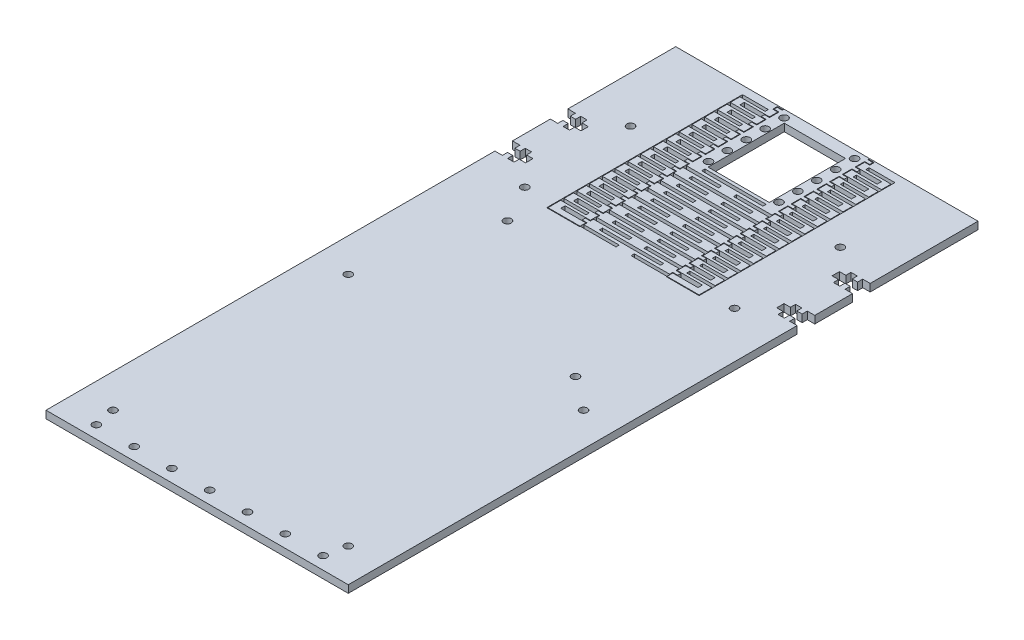
SolidWorks part; units mm, degrees
ref_plane "Front Plane" through (0, 0, 0) normal (0, 0, 1) x (1, 0, 0)
ref_plane "Top Plane" through (0, 0, 0) normal (0, 1, 0) x (1, 0, 0)
ref_plane "Right Plane" through (0, 0, 0) normal (1, 0, 0) x (0, 0, -1)
sketch "Sketch1" plane through (0, 0, 0) normal (0, 1, 0) x (1, 0, 0)
  line L0 (0, 250) -> (0, 0) construction
  line L1 (-60, 250) -> (60, 250)
  line L2 (-60, 250) -> (-60, 0)
  line L3 (-60, 0) -> (60, 0)
  line L4 (60, 250) -> (60, 0)
  circle A0 centre (46.7, 13.3) radius 1.5
  circle A3 centre (46.7, 106.7) radius 1.5
  circle A4 centre (-46.7, 13.3) radius 1.5
  circle A5 centre (-46.7, 106.7) radius 1.5
  circle A6 centre (-41.6382, 213.7) radius 1.5
  circle A7 centre (-41.6382, 171.7) radius 1.5
  circle A10 centre (41.6382, 171.7) radius 1.5
  circle A11 centre (41.6382, 213.7) radius 1.5
  circle A12 centre (33.5, 116.7) radius 1.5
  circle A13 centre (-33.5, 156.7) radius 1.5
  circle A14 centre (-45, 5) radius 1.5
  circle A15 centre (-30, 5) radius 1.5
  circle A16 centre (-15, 5) radius 1.5
  circle A17 centre (0, 5) radius 1.5
  circle A18 centre (45, 5) radius 1.5
  circle A19 centre (30, 5) radius 1.5
  circle A20 centre (15, 5) radius 1.5
  line B0 (-60, 207.1925) -> (-57.0282, 207.1925)
  line B1 (-57.0282, 207.1925) -> (-57.0282, 205.1605)
  line B2 (-57.0282, 205.1605) -> (-54.92, 205.1605)
  line B3 (-54.92, 205.1605) -> (-54.92, 207.1925)
  line B4 (-54.92, 207.1925) -> (-52.38, 207.1925)
  line B5 (-52.38, 207.1925) -> (-52.38, 205.1605)
  line B6 (-52.38, 205.1605) -> (-49.84, 205.1605)
  line B7 (-49.84, 205.1605) -> (-49.84, 202.2395)
  line B8 (-60, 200.2075) -> (-57.0282, 200.2075)
  line B9 (-57.0282, 200.2075) -> (-57.0282, 202.2395)
  line B10 (-57.0282, 202.2395) -> (-54.92, 202.2395)
  line B11 (-54.92, 202.2395) -> (-54.92, 200.2075)
  line B12 (-54.92, 200.2075) -> (-52.38, 200.2075)
  line B13 (-52.38, 200.2075) -> (-52.38, 202.2395)
  line B14 (-52.38, 202.2395) -> (-49.84, 202.2395)
  line B15 (-60, 185.1925) -> (-57.0282, 185.1925)
  line B16 (-57.0282, 185.1925) -> (-57.0282, 183.1605)
  line B17 (-57.0282, 183.1605) -> (-54.92, 183.1605)
  line B18 (-54.92, 183.1605) -> (-54.92, 185.1925)
  line B19 (-54.92, 185.1925) -> (-52.38, 185.1925)
  line B20 (-52.38, 185.1925) -> (-52.38, 183.1605)
  line B21 (-52.38, 183.1605) -> (-49.84, 183.1605)
  line B22 (-49.84, 183.1605) -> (-49.84, 180.2395)
  line B23 (-60, 178.2075) -> (-57.0282, 178.2075)
  line B24 (-57.0282, 178.2075) -> (-57.0282, 180.2395)
  line B25 (-57.0282, 180.2395) -> (-54.92, 180.2395)
  line B26 (-54.92, 180.2395) -> (-54.92, 178.2075)
  line B27 (-54.92, 178.2075) -> (-52.38, 178.2075)
  line B28 (-52.38, 178.2075) -> (-52.38, 180.2395)
  line B29 (-52.38, 180.2395) -> (-49.84, 180.2395)
  line B30 (60, 185.1925) -> (57.0282, 185.1925)
  line B31 (57.0282, 185.1925) -> (57.0282, 183.1605)
  line B32 (57.0282, 183.1605) -> (54.92, 183.1605)
  line B33 (54.92, 183.1605) -> (54.92, 185.1925)
  line B34 (54.92, 185.1925) -> (52.38, 185.1925)
  line B35 (52.38, 185.1925) -> (52.38, 183.1605)
  line B36 (52.38, 183.1605) -> (49.84, 183.1605)
  line B37 (49.84, 183.1605) -> (49.84, 180.2395)
  line B38 (60, 178.2075) -> (57.0282, 178.2075)
  line B39 (57.0282, 178.2075) -> (57.0282, 180.2395)
  line B40 (57.0282, 180.2395) -> (54.92, 180.2395)
  line B41 (54.92, 180.2395) -> (54.92, 178.2075)
  line B42 (54.92, 178.2075) -> (52.38, 178.2075)
  line B43 (52.38, 178.2075) -> (52.38, 180.2395)
  line B44 (52.38, 180.2395) -> (49.84, 180.2395)
  line B45 (60, 207.1925) -> (57.0282, 207.1925)
  line B46 (57.0282, 207.1925) -> (57.0282, 205.1605)
  line B47 (57.0282, 205.1605) -> (54.92, 205.1605)
  line B48 (54.92, 205.1605) -> (54.92, 207.1925)
  line B49 (54.92, 207.1925) -> (52.38, 207.1925)
  line B50 (52.38, 207.1925) -> (52.38, 205.1605)
  line B51 (52.38, 205.1605) -> (49.84, 205.1605)
  line B52 (49.84, 205.1605) -> (49.84, 202.2395)
  line B53 (60, 200.2075) -> (57.0282, 200.2075)
  line B54 (57.0282, 200.2075) -> (57.0282, 202.2395)
  line B55 (57.0282, 202.2395) -> (54.92, 202.2395)
  line B56 (54.92, 202.2395) -> (54.92, 200.2075)
  line B57 (54.92, 200.2075) -> (52.38, 200.2075)
  line B58 (52.38, 200.2075) -> (52.38, 202.2395)
  line B59 (52.38, 202.2395) -> (49.84, 202.2395)
  dimension "D3" = 3
  dimension "D8" = 3
  dimension "D1" = 120
  dimension "D2" = 250
  dimension "D4" = 13.3
  dimension "D5" = 13.3
  dimension "D6" = 93.4
  dimension "D7" = 42
  dimension "D9" = 18.3618
  dimension "D10" = 15
  dimension "D11" = 33.5
  dimension "D12" = 67
  dimension "D13" = 40
  dimension "D14" = 10
  dimension "D15" = 10
  dimension "D16" = 10
  dimension "D17" = 15
  dimension "D18" = 15
  dimension "D19" = 15
  dimension "D20" = 5
sketch_block_instance "Block4-1"
sketch_block "Block4" parameters "D1"=1.4605, "D2"=2.9718
sketch_block_instance "Block4-2"
sketch_block_instance "Block4-3"
sketch_block_instance "Block4-4"
extrude "Boss-Extrude1" add sketch "Sketch1" along normal blind 2.9718 contours L1 L0 L3 L4 A11 A0 A3 A10 A12 | L0 L1 L2 B0 B1 B2 B3 B4 B5 B6 B7 B14 B13 B12 B11 B10 B9 B8 B15 B16 B17 B18 B19 B20 B21 B22 B29 B28 B27 B26 B25 B24 B23 L3 A13 A7 A6 A4 A5 region at (0, 0, -124.7167)
sketch "Sketch2" plane through (0, 2.9718, 0) normal (0, 1, 0) x (1, 0, 0)
  line L0 (-30, 250) -> (-30, 165) construction
  line L1 (-60, 250) -> (60, 250) construction
  line L2 (-30, 165) -> (30, 165) construction
  line L3 (30, 165) -> (30, 250) construction
  line L4 (0, 250) -> (0, 0) construction
  line L5 (-17, 250) -> (17, 250)
  line L7 (-17, 215) -> (17, 215)
  line L8 (17, 250) -> (17, 215)
  line L10 (-12.15, 215) -> (12.15, 215)
  line L11 (-12.15, 215) -> (-12.15, 245.25)
  line L12 (-12.15, 245.25) -> (12.15, 245.25)
  line L13 (12.15, 215) -> (12.15, 245.25)
  line L14 (-12.15, 213.73) -> (12.15, 213.73)
  line L15 (-12.15, 213.73) -> (-12.15, 212.46)
  line L16 (-12.15, 212.46) -> (12.15, 212.46)
  line L17 (12.15, 213.73) -> (12.15, 212.46)
  line L18 (-17, 211.19) -> (-3, 211.19)
  line L20 (-17, 209.92) -> (-3, 209.92)
  line L21 (-3, 211.19) -> (-3, 209.92)
  line L22 (3, 211.19) -> (3, 209.92)
  line L23 (17, 209.92) -> (3, 209.92)
  line L24 (17, 211.19) -> (3, 211.19)
  line L25 (12.15, 215) -> (12.15, 245.25)
  line L26 (-17, 217.54) -> (-17, 216.27)
  line L27 (17.25, 250) -> (17.25, 249.54)
  line L28 (-17, 215) -> (-17, 213.73)
  line L29 (-17, 213.73) -> (-19, 213.73)
  line L30 (-19, 213.73) -> (-19, 212.46)
  line L31 (-19, 212.46) -> (-17, 212.46)
  line L32 (-17, 212.46) -> (-17, 211.19)
  line L33 (-17.25, 215) -> (-17.25, 213.98)
  line L34 (-17.25, 213.98) -> (-19.25, 213.98)
  line L35 (-30.25, 250) -> (-30.25, 165)
  line L36 (-19.25, 212.21) -> (-17.25, 212.21)
  line L37 (-17.25, 212.21) -> (-17.25, 211.19)
  line L38 (19, 213.73) -> (19, 212.46)
  line L39 (19, 212.46) -> (17, 212.46)
  line L40 (17, 212.46) -> (17, 211.19)
  line L41 (17, 215) -> (17, 213.73)
  line L42 (17, 213.73) -> (19, 213.73)
  line L43 (19.25, 213.98) -> (19.25, 212.21)
  line L44 (19.25, 212.21) -> (17.25, 212.21)
  line L45 (17.25, 212.21) -> (17.25, 211.19)
  line L46 (17.25, 213.98) -> (19.25, 213.98)
  line L47 (17.25, 215) -> (17.25, 213.98)
  line L48 (-17.25, 211.19) -> (-17.25, 209.92)
  line L49 (17.25, 211.19) -> (17.25, 209.92)
  line L50 (-17.25, 209.92) -> (-17.25, 208.9)
  line L51 (-17, 209.92) -> (-17, 208.65)
  line L52 (17.25, 250) -> (17, 250)
  line L53 (-17, 250) -> (-17.25, 250)
  line L54 (-17, 208.65) -> (-19, 208.65)
  line L55 (-17.25, 208.9) -> (-19.25, 208.9)
  line L56 (-19, 208.65) -> (-19, 207.38)
  line L57 (-30, 250) -> (-30, 246.75)
  line L58 (-19, 207.38) -> (-17, 207.38)
  line L59 (-19.25, 207.13) -> (-17.25, 207.13)
  line L60 (-17, 207.38) -> (-17, 206.11)
  line L61 (-17, 206.11) -> (-3, 206.11)
  line L62 (-17, 204.84) -> (-3, 204.84)
  line L63 (-17.25, 206.11) -> (-17.25, 204.84)
  line L64 (-12.15, 207.38) -> (12.15, 207.38)
  line L65 (-17.25, 207.13) -> (-17.25, 206.11)
  line L66 (-3, 206.11) -> (-3, 204.84)
  line L67 (17, 206.11) -> (3, 206.11)
  line L68 (3, 206.11) -> (3, 204.84)
  line L69 (17, 204.84) -> (3, 204.84)
  line L70 (-12.15, 208.65) -> (12.15, 208.65)
  line L71 (-12.15, 208.65) -> (-12.15, 207.38)
  line L72 (12.15, 208.65) -> (12.15, 207.38)
  line L73 (17.25, 209.92) -> (17.25, 208.9)
  line L74 (17, 209.92) -> (17, 208.65)
  line L75 (17.25, 208.9) -> (19.25, 208.9)
  line L76 (17, 208.65) -> (19, 208.65)
  line L77 (19.25, 208.9) -> (19.25, 207.13)
  line L78 (19, 208.65) -> (19, 207.38)
  line L79 (19, 207.38) -> (17, 207.38)
  line L80 (19.25, 207.13) -> (17.25, 207.13)
  line L81 (17, 207.38) -> (17, 206.11)
  line L82 (17.25, 207.13) -> (17.25, 206.11)
  line L83 (17.25, 206.11) -> (17.25, 204.84)
  line L84 (-17.25, 204.84) -> (-17.25, 203.82)
  line L85 (-17, 204.84) -> (-17, 203.57)
  line L86 (-17, 203.57) -> (-19, 203.57)
  line L87 (-17.25, 203.82) -> (-19.25, 203.82)
  line L88 (-19, 203.57) -> (-19, 202.3)
  line L89 (-30, 245.48) -> (-30, 241.67)
  line L90 (-19, 202.3) -> (-17, 202.3)
  line L91 (-19.25, 202.05) -> (-17.25, 202.05)
  line L92 (-17, 202.3) -> (-17, 201.03)
  line L93 (-17, 201.03) -> (-3, 201.03)
  line L94 (-17, 199.76) -> (-3, 199.76)
  line L95 (-17.25, 201.03) -> (-17.25, 199.76)
  line L96 (-12.15, 202.3) -> (12.15, 202.3)
  line L97 (-17.25, 202.05) -> (-17.25, 201.03)
  line L98 (-3, 201.03) -> (-3, 199.76)
  line L99 (17, 201.03) -> (3, 201.03)
  line L100 (3, 201.03) -> (3, 199.76)
  line L101 (17, 199.76) -> (3, 199.76)
  line L102 (-12.15, 203.57) -> (12.15, 203.57)
  line L103 (-12.15, 203.57) -> (-12.15, 202.3)
  line L104 (12.15, 203.57) -> (12.15, 202.3)
  line L105 (17.25, 204.84) -> (17.25, 203.82)
  line L106 (17, 204.84) -> (17, 203.57)
  line L107 (17.25, 203.82) -> (19.25, 203.82)
  line L108 (17, 203.57) -> (19, 203.57)
  line L109 (19.25, 203.82) -> (19.25, 202.05)
  line L110 (19, 203.57) -> (19, 202.3)
  line L111 (19, 202.3) -> (17, 202.3)
  line L112 (19.25, 202.05) -> (17.25, 202.05)
  line L113 (17, 202.3) -> (17, 201.03)
  line L114 (17.25, 202.05) -> (17.25, 201.03)
  line L115 (17.25, 201.03) -> (17.25, 199.76)
  line L116 (-17.25, 199.76) -> (-17.25, 198.74)
  line L117 (-17, 199.76) -> (-17, 198.49)
  line L118 (-17, 198.49) -> (-19, 198.49)
  line L119 (-17.25, 198.74) -> (-19.25, 198.74)
  line L120 (-19, 198.49) -> (-19, 197.22)
  line L121 (-30, 244.92) -> (-30, 241.67)
  line L122 (-19, 197.22) -> (-17, 197.22)
  line L123 (-19.25, 196.97) -> (-17.25, 196.97)
  line L124 (-17, 197.22) -> (-17, 195.95)
  line L125 (-17, 195.95) -> (-3, 195.95)
  line L126 (-17, 194.68) -> (-3, 194.68)
  line L127 (-17.25, 195.95) -> (-17.25, 194.68)
  line L128 (-12.15, 197.22) -> (12.15, 197.22)
  line L129 (-17.25, 196.97) -> (-17.25, 195.95)
  line L130 (-3, 195.95) -> (-3, 194.68)
  line L131 (17, 195.95) -> (3, 195.95)
  line L132 (3, 195.95) -> (3, 194.68)
  line L133 (17, 194.68) -> (3, 194.68)
  line L134 (-12.15, 198.49) -> (12.15, 198.49)
  line L135 (-12.15, 198.49) -> (-12.15, 197.22)
  line L136 (12.15, 198.49) -> (12.15, 197.22)
  line L137 (17.25, 199.76) -> (17.25, 198.74)
  line L138 (17, 199.76) -> (17, 198.49)
  line L139 (17.25, 198.74) -> (19.25, 198.74)
  line L140 (17, 198.49) -> (19, 198.49)
  line L141 (19.25, 198.74) -> (19.25, 196.97)
  line L142 (19, 198.49) -> (19, 197.22)
  line L143 (19, 197.22) -> (17, 197.22)
  line L144 (19.25, 196.97) -> (17.25, 196.97)
  line L145 (17, 197.22) -> (17, 195.95)
  line L146 (17.25, 196.97) -> (17.25, 195.95)
  line L147 (17.25, 195.95) -> (17.25, 194.68)
  line L148 (-17.25, 194.68) -> (-17.25, 193.66)
  line L149 (-17, 194.68) -> (-17, 193.41)
  line L150 (-17, 193.41) -> (-19, 193.41)
  line L151 (-17.25, 193.66) -> (-19.25, 193.66)
  line L152 (-19, 193.41) -> (-19, 192.14)
  line L153 (-30, 240.4) -> (-30, 236.59)
  line L154 (-19, 192.14) -> (-17, 192.14)
  line L155 (-19.25, 191.89) -> (-17.25, 191.89)
  line L156 (-17, 192.14) -> (-17, 190.87)
  line L157 (-17, 190.87) -> (-3, 190.87)
  line L158 (-17, 189.6) -> (-3, 189.6)
  line L159 (-17.25, 190.87) -> (-17.25, 189.6)
  line L160 (-12.15, 192.14) -> (12.15, 192.14)
  line L161 (-17.25, 191.89) -> (-17.25, 190.87)
  line L162 (-3, 190.87) -> (-3, 189.6)
  line L163 (17, 190.87) -> (3, 190.87)
  line L164 (3, 190.87) -> (3, 189.6)
  line L165 (17, 189.6) -> (3, 189.6)
  line L166 (-12.15, 193.41) -> (12.15, 193.41)
  line L167 (-12.15, 193.41) -> (-12.15, 192.14)
  line L168 (12.15, 193.41) -> (12.15, 192.14)
  line L169 (17.25, 194.68) -> (17.25, 193.66)
  line L170 (17, 194.68) -> (17, 193.41)
  line L171 (17.25, 193.66) -> (19.25, 193.66)
  line L172 (17, 193.41) -> (19, 193.41)
  line L173 (19.25, 193.66) -> (19.25, 191.89)
  line L174 (19, 193.41) -> (19, 192.14)
  line L175 (19, 192.14) -> (17, 192.14)
  line L176 (19.25, 191.89) -> (17.25, 191.89)
  line L177 (17, 192.14) -> (17, 190.87)
  line L178 (17.25, 191.89) -> (17.25, 190.87)
  line L179 (17.25, 190.87) -> (17.25, 189.6)
  line L180 (-17.25, 189.6) -> (-17.25, 188.58)
  line L181 (-17, 189.6) -> (-17, 188.33)
  line L182 (-17, 188.33) -> (-19, 188.33)
  line L183 (-17.25, 188.58) -> (-19.25, 188.58)
  line L184 (-19, 188.33) -> (-19, 187.06)
  line L185 (-30, 239.84) -> (-30, 236.59)
  line L186 (-19, 187.06) -> (-17, 187.06)
  line L187 (-19.25, 186.81) -> (-17.25, 186.81)
  line L188 (-17, 187.06) -> (-17, 185.79)
  line L189 (-17, 185.79) -> (-3, 185.79)
  line L190 (-17, 184.52) -> (-3, 184.52)
  line L191 (-17.25, 185.79) -> (-17.25, 184.52)
  line L192 (-12.15, 187.06) -> (12.15, 187.06)
  line L193 (-17.25, 186.81) -> (-17.25, 185.79)
  line L194 (-3, 185.79) -> (-3, 184.52)
  line L195 (17, 185.79) -> (3, 185.79)
  line L196 (3, 185.79) -> (3, 184.52)
  line L197 (17, 184.52) -> (3, 184.52)
  line L198 (-12.15, 188.33) -> (12.15, 188.33)
  line L199 (-12.15, 188.33) -> (-12.15, 187.06)
  line L200 (12.15, 188.33) -> (12.15, 187.06)
  line L201 (17.25, 189.6) -> (17.25, 188.58)
  line L202 (17, 189.6) -> (17, 188.33)
  line L203 (17.25, 188.58) -> (19.25, 188.58)
  line L204 (17, 188.33) -> (19, 188.33)
  line L205 (19.25, 188.58) -> (19.25, 186.81)
  line L206 (19, 188.33) -> (19, 187.06)
  line L207 (19, 187.06) -> (17, 187.06)
  line L208 (19.25, 186.81) -> (17.25, 186.81)
  line L209 (17, 187.06) -> (17, 185.79)
  line L210 (17.25, 186.81) -> (17.25, 185.79)
  line L211 (17.25, 185.79) -> (17.25, 184.52)
  line L212 (-17.25, 184.52) -> (-17.25, 183.5)
  line L213 (-17, 184.52) -> (-17, 183.25)
  line L214 (-17, 183.25) -> (-19, 183.25)
  line L215 (-17.25, 183.5) -> (-19.25, 183.5)
  line L216 (-19, 183.25) -> (-19, 181.98)
  line L217 (-30, 235.32) -> (-30, 231.51)
  line L218 (-19, 181.98) -> (-17, 181.98)
  line L219 (-19.25, 181.73) -> (-17.25, 181.73)
  line L220 (-17, 181.98) -> (-17, 180.71)
  line L221 (-17, 180.71) -> (-3, 180.71)
  line L222 (-17, 179.44) -> (-3, 179.44)
  line L223 (-17.25, 180.71) -> (-17.25, 179.44)
  line L224 (-12.15, 181.98) -> (12.15, 181.98)
  line L225 (-17.25, 181.73) -> (-17.25, 180.71)
  line L226 (-3, 180.71) -> (-3, 179.44)
  line L227 (17, 180.71) -> (3, 180.71)
  line L228 (3, 180.71) -> (3, 179.44)
  line L229 (17, 179.44) -> (3, 179.44)
  line L230 (-12.15, 183.25) -> (12.15, 183.25)
  line L231 (-12.15, 183.25) -> (-12.15, 181.98)
  line L232 (12.15, 183.25) -> (12.15, 181.98)
  line L233 (17.25, 184.52) -> (17.25, 183.5)
  line L234 (17, 184.52) -> (17, 183.25)
  line L235 (17.25, 183.5) -> (19.25, 183.5)
  line L236 (17, 183.25) -> (19, 183.25)
  line L237 (19.25, 183.5) -> (19.25, 181.73)
  line L238 (19, 183.25) -> (19, 181.98)
  line L239 (19, 181.98) -> (17, 181.98)
  line L240 (19.25, 181.73) -> (17.25, 181.73)
  line L241 (17, 181.98) -> (17, 180.71)
  line L242 (17.25, 181.73) -> (17.25, 180.71)
  line L243 (17.25, 180.71) -> (17.25, 179.44)
  line L244 (-17.25, 179.44) -> (-17.25, 178.42)
  line L245 (-17, 179.44) -> (-17, 178.17)
  line L246 (-17, 178.17) -> (-19, 178.17)
  line L247 (-17.25, 178.42) -> (-19.25, 178.42)
  line L248 (-19, 178.17) -> (-19, 176.9)
  line L249 (-30, 234.76) -> (-30, 231.51)
  line L250 (-19, 176.9) -> (-17, 176.9)
  line L251 (-19.25, 176.65) -> (-17.25, 176.65)
  line L252 (-17, 176.9) -> (-17, 175.63)
  line L253 (-17, 175.63) -> (-3, 175.63)
  line L254 (-17, 174.36) -> (-3, 174.36)
  line L255 (-17.25, 175.63) -> (-17.25, 174.36)
  line L256 (-12.15, 176.9) -> (12.15, 176.9)
  line L257 (-17.25, 176.65) -> (-17.25, 175.63)
  line L258 (-3, 175.63) -> (-3, 174.36)
  line L259 (17, 175.63) -> (3, 175.63)
  line L260 (3, 175.63) -> (3, 174.36)
  line L261 (17, 174.36) -> (3, 174.36)
  line L262 (-12.15, 178.17) -> (12.15, 178.17)
  line L263 (-12.15, 178.17) -> (-12.15, 176.9)
  line L264 (12.15, 178.17) -> (12.15, 176.9)
  line L265 (17.25, 179.44) -> (17.25, 178.42)
  line L266 (17, 179.44) -> (17, 178.17)
  line L267 (17.25, 178.42) -> (19.25, 178.42)
  line L268 (17, 178.17) -> (19, 178.17)
  line L269 (19.25, 178.42) -> (19.25, 176.65)
  line L270 (19, 178.17) -> (19, 176.9)
  line L271 (19, 176.9) -> (17, 176.9)
  line L272 (19.25, 176.65) -> (17.25, 176.65)
  line L273 (17, 176.9) -> (17, 175.63)
  line L274 (17.25, 176.65) -> (17.25, 175.63)
  line L275 (17.25, 175.63) -> (17.25, 174.36)
  line L276 (-17.25, 174.36) -> (-17.25, 173.34)
  line L277 (-17, 174.36) -> (-17, 173.09)
  line L278 (-17, 173.09) -> (-19, 173.09)
  line L279 (-17.25, 173.34) -> (-19.25, 173.34)
  line L280 (-19, 173.09) -> (-19, 171.82)
  line L281 (-30, 230.24) -> (-30, 226.43)
  line L282 (-19, 171.82) -> (-17, 171.82)
  line L283 (-19.25, 171.57) -> (-17.25, 171.57)
  line L284 (-17, 171.82) -> (-17, 170.55)
  line L285 (-17, 170.55) -> (-3, 170.55)
  line L286 (-17, 169.28) -> (-3, 169.28)
  line L287 (-17.25, 170.55) -> (-17.25, 169.28)
  line L288 (-12.15, 171.82) -> (12.15, 171.82)
  line L289 (-17.25, 171.57) -> (-17.25, 170.55)
  line L290 (-3, 170.55) -> (-3, 169.28)
  line L291 (17, 170.55) -> (3, 170.55)
  line L292 (3, 170.55) -> (3, 169.28)
  line L293 (17, 169.28) -> (3, 169.28)
  line L294 (-12.15, 173.09) -> (12.15, 173.09)
  line L295 (-12.15, 173.09) -> (-12.15, 171.82)
  line L296 (12.15, 173.09) -> (12.15, 171.82)
  line L297 (17.25, 174.36) -> (17.25, 173.34)
  line L298 (17, 174.36) -> (17, 173.09)
  line L299 (17.25, 173.34) -> (19.25, 173.34)
  line L300 (17, 173.09) -> (19, 173.09)
  line L301 (19.25, 173.34) -> (19.25, 171.57)
  line L302 (19, 173.09) -> (19, 171.82)
  line L303 (19, 171.82) -> (17, 171.82)
  line L304 (19.25, 171.57) -> (17.25, 171.57)
  line L305 (17, 171.82) -> (17, 170.55)
  line L306 (17.25, 171.57) -> (17.25, 170.55)
  line L307 (17.25, 170.55) -> (17.25, 169.28)
  line L308 (-17, 169.28) -> (-17.25, 169.28)
  line L309 (17.25, 169.28) -> (17, 169.28)
  line L310 (-17.25, 217.29) -> (-17.25, 216.27)
  line L315 (-19.25, 217.29) -> (-17.25, 217.29)
  line L316 (-19, 217.54) -> (-17, 217.54)
  line L317 (-30, 229.68) -> (-30, 226.43)
  line L318 (-19, 218.81) -> (-19, 217.54)
  line L319 (-17, 218.81) -> (-19, 218.81)
  line L320 (-17.25, 219.06) -> (-19.25, 219.06)
  line L321 (-17, 220.08) -> (-17, 218.81)
  line L322 (-17.25, 220.08) -> (-17.25, 219.06)
  line L323 (-17, 222.62) -> (-17, 221.35)
  line L324 (-17.25, 222.37) -> (-17.25, 221.35)
  line L325 (-19.25, 222.37) -> (-17.25, 222.37)
  line L326 (-19, 222.62) -> (-17, 222.62)
  line L327 (-30, 225.16) -> (-30, 221.35)
  line L328 (-19, 223.89) -> (-19, 222.62)
  line L329 (-17, 223.89) -> (-19, 223.89)
  line L330 (-17.25, 224.14) -> (-19.25, 224.14)
  line L331 (-17, 225.16) -> (-17, 223.89)
  line L332 (-17.25, 225.16) -> (-17.25, 224.14)
  line L333 (-17, 227.7) -> (-17, 226.43)
  line L334 (-17.25, 227.45) -> (-17.25, 226.43)
  line L335 (-19.25, 227.45) -> (-17.25, 227.45)
  line L336 (-19, 227.7) -> (-17, 227.7)
  line L337 (-30, 224.6) -> (-30, 221.35)
  line L338 (-19, 228.97) -> (-19, 227.7)
  line L339 (-17, 228.97) -> (-19, 228.97)
  line L340 (-17.25, 229.22) -> (-19.25, 229.22)
  line L341 (-17, 230.24) -> (-17, 228.97)
  line L342 (-17.25, 230.24) -> (-17.25, 229.22)
  line L343 (-17, 232.78) -> (-17, 231.51)
  line L344 (-17.25, 232.53) -> (-17.25, 231.51)
  line L345 (-19.25, 232.53) -> (-17.25, 232.53)
  line L346 (-19, 232.78) -> (-17, 232.78)
  line L347 (-30, 220.08) -> (-30, 216.27)
  line L348 (-19, 234.05) -> (-19, 232.78)
  line L349 (-17, 234.05) -> (-19, 234.05)
  line L350 (-17.25, 234.3) -> (-19.25, 234.3)
  line L351 (-17, 235.32) -> (-17, 234.05)
  line L352 (-17.25, 235.32) -> (-17.25, 234.3)
  line L353 (-17, 237.86) -> (-17, 236.59)
  line L354 (-17.25, 237.61) -> (-17.25, 236.59)
  line L355 (-19.25, 237.61) -> (-17.25, 237.61)
  line L356 (-19, 237.86) -> (-17, 237.86)
  line L357 (-30, 219.52) -> (-30, 216.27)
  line L358 (-19, 239.13) -> (-19, 237.86)
  line L359 (-17, 239.13) -> (-19, 239.13)
  line L360 (-17.25, 239.38) -> (-19.25, 239.38)
  line L361 (-17, 240.4) -> (-17, 239.13)
  line L362 (-17.25, 240.4) -> (-17.25, 239.38)
  line L363 (-17, 242.94) -> (-17, 241.67)
  line L364 (-17.25, 242.69) -> (-17.25, 241.67)
  line L365 (-19.25, 242.69) -> (-17.25, 242.69)
  line L366 (-19, 242.94) -> (-17, 242.94)
  line L367 (-20, 240.4) -> (-20, 241.67)
  line L368 (-19, 244.21) -> (-19, 242.94)
  line L369 (-17, 244.21) -> (-19, 244.21)
  line L370 (-17.25, 244.46) -> (-19.25, 244.46)
  line L371 (-17, 245.48) -> (-17, 244.21)
  line L372 (-17.25, 245.48) -> (-17.25, 244.46)
  line L373 (-17, 248.02) -> (-17, 246.75)
  line L374 (-17.25, 247.77) -> (-17.25, 246.75)
  line L375 (-19.25, 247.77) -> (-17.25, 247.77)
  line L376 (-19, 248.02) -> (-17, 248.02)
  line L377 (-19.25, 249.54) -> (-19.25, 247.77)
  line L378 (-19, 249.29) -> (-19, 248.02)
  line L379 (-17, 249.29) -> (-19, 249.29)
  line L380 (-17.25, 249.54) -> (-19.25, 249.54)
  line L381 (-17.25, 215) -> (-17.25, 216.27)
  line L382 (-17, 215) -> (-17, 216.27)
  line L383 (-17, 221.35) -> (-17, 220.08)
  line L384 (-17.25, 250.56) -> (-17.25, 249.54) [skipped]
  line L385 (-17, 250.56) -> (-17, 249.29) [skipped]
  line L386 (-17, 216.27) -> (-17, 215)
  line L387 (-17.25, 220.08) -> (-17.25, 221.35)
  line L388 (-17, 226.43) -> (-17, 225.16)
  line L389 (-17.25, 226.43) -> (-17.25, 225.16)
  line L390 (-17, 231.51) -> (-17, 230.24)
  line L391 (-17.25, 231.51) -> (-17.25, 230.24)
  line L392 (-17, 236.59) -> (-17, 235.32)
  line L393 (-17.25, 236.59) -> (-17.25, 235.32)
  line L394 (-17, 241.67) -> (-17, 240.4)
  line L395 (-17.25, 241.67) -> (-17.25, 240.4)
  line L396 (-17, 246.75) -> (-17, 245.48)
  line L397 (-17.25, 246.75) -> (-17.25, 245.48)
  line L398 (-17, 249.29) -> (-17, 250)
  line L399 (-17.25, 250) -> (-17.25, 249.54)
  line L400 (17, 249.29) -> (17, 250)
  line L401 (17.25, 246.75) -> (17.25, 245.48)
  line L402 (17, 246.75) -> (17, 245.48)
  line L403 (17.25, 249.54) -> (19.25, 249.54)
  line L404 (17, 249.29) -> (19, 249.29)
  line L405 (19, 249.29) -> (19, 248.02)
  line L406 (19.25, 249.54) -> (19.25, 247.77)
  line L407 (19, 248.02) -> (17, 248.02)
  line L408 (19.25, 247.77) -> (17.25, 247.77)
  line L409 (17.25, 247.77) -> (17.25, 246.75)
  line L410 (17, 248.02) -> (17, 246.75)
  line L411 (17.25, 245.48) -> (17.25, 244.46)
  line L412 (17, 245.48) -> (17, 244.21)
  line L413 (17.25, 244.46) -> (19.25, 244.46)
  line L414 (17, 244.21) -> (19, 244.21)
  line L415 (17, 250) -> (17.25, 250)
  line L416 (17.25, 241.67) -> (17.25, 240.4)
  line L417 (17, 241.67) -> (17, 240.4)
  line L418 (17.25, 236.59) -> (17.25, 235.32)
  line L419 (17, 236.59) -> (17, 235.32)
  line L420 (17.25, 231.51) -> (17.25, 230.24)
  line L421 (17, 231.51) -> (17, 230.24)
  line L422 (19, 244.21) -> (19, 242.94)
  line L423 (19.25, 244.46) -> (19.25, 242.69)
  line L424 (19, 242.94) -> (17, 242.94)
  line L425 (19.25, 242.69) -> (17.25, 242.69)
  line L426 (17.25, 242.69) -> (17.25, 241.67)
  line L427 (17, 242.94) -> (17, 241.67)
  line L428 (17.25, 240.4) -> (17.25, 239.38)
  line L429 (17, 240.4) -> (17, 239.13)
  line L430 (17.25, 239.38) -> (19.25, 239.38)
  line L431 (17, 239.13) -> (19, 239.13)
  line L432 (19, 239.13) -> (19, 237.86)
  line L433 (19.25, 239.38) -> (19.25, 237.61)
  line L434 (19, 237.86) -> (17, 237.86)
  line L435 (19.25, 237.61) -> (17.25, 237.61)
  line L436 (17.25, 237.61) -> (17.25, 236.59)
  line L437 (17, 237.86) -> (17, 236.59)
  line L438 (17.25, 235.32) -> (17.25, 234.3)
  line L439 (17, 235.32) -> (17, 234.05)
  line L440 (17.25, 234.3) -> (19.25, 234.3)
  line L441 (17, 234.05) -> (19, 234.05)
  line L442 (19, 234.05) -> (19, 232.78)
  line L443 (19.25, 234.3) -> (19.25, 232.53)
  line L444 (19, 232.78) -> (17, 232.78)
  line L445 (19.25, 232.53) -> (17.25, 232.53)
  line L446 (17.25, 232.53) -> (17.25, 231.51)
  line L447 (17, 232.78) -> (17, 231.51)
  line L448 (17.25, 230.24) -> (17.25, 229.22)
  line L449 (17, 230.24) -> (17, 228.97)
  line L450 (17.25, 229.22) -> (19.25, 229.22)
  line L451 (17, 228.97) -> (19, 228.97)
  line L452 (17.25, 226.43) -> (17.25, 225.16)
  line L453 (17, 226.43) -> (17, 225.16)
  line L454 (17.25, 220.08) -> (17.25, 221.35)
  line L455 (17, 221.35) -> (17, 220.08)
  line L456 (19, 228.97) -> (19, 227.7)
  line L457 (19.25, 229.22) -> (19.25, 227.45)
  line L458 (19, 227.7) -> (17, 227.7)
  line L459 (19.25, 227.45) -> (17.25, 227.45)
  line L460 (17.25, 227.45) -> (17.25, 226.43)
  line L461 (17, 227.7) -> (17, 226.43)
  line L462 (17.25, 225.16) -> (17.25, 224.14)
  line L463 (17, 225.16) -> (17, 223.89)
  line L464 (17.25, 224.14) -> (19.25, 224.14)
  line L465 (17, 223.89) -> (19, 223.89)
  line L466 (19, 223.89) -> (19, 222.62)
  line L467 (19.25, 224.14) -> (19.25, 222.37)
  line L468 (19, 222.62) -> (17, 222.62)
  line L469 (19.25, 222.37) -> (17.25, 222.37)
  line L470 (17.25, 222.37) -> (17.25, 221.35)
  line L471 (17, 222.62) -> (17, 221.35)
  line L472 (17.25, 220.08) -> (17.25, 219.06)
  line L473 (17, 220.08) -> (17, 218.81)
  line L474 (17, 218.81) -> (19, 218.81)
  line L475 (17.25, 219.06) -> (19.25, 219.06)
  line L476 (19, 218.81) -> (19, 217.54)
  line L477 (19.25, 219.06) -> (19.25, 217.29)
  line L478 (19.25, 217.29) -> (17.25, 217.29)
  line L479 (19, 217.54) -> (17, 217.54)
  line L480 (17.25, 217.29) -> (17.25, 216.27)
  line L481 (17, 217.54) -> (17, 216.27)
  line L482 (17, 215) -> (17, 216.27)
  line L483 (17.25, 215) -> (17.25, 216.27)
  line L484 (-20, 240.4) -> (-30, 240.4)
  line L485 (-20, 245.48) -> (-30, 245.48)
  line L486 (-20, 245.48) -> (-20, 246.75)
  line L487 (-20, 246.75) -> (-30, 246.75)
  line L489 (-19.25, 244.46) -> (-27.25, 244.46)
  line L491 (-19.25, 242.69) -> (-27.25, 242.69)
  line L492 (-27.25, 244.46) -> (-27.25, 242.69)
  line L493 (-30.25, 250) -> (-30, 250)
  line L494 (-20, 241.67) -> (-30, 241.67)
  line L495 (-19.25, 239.38) -> (-27.25, 239.38)
  line L496 (-27.25, 239.38) -> (-27.25, 237.61)
  line L497 (-19.25, 237.61) -> (-27.25, 237.61)
  line L498 (-20, 235.32) -> (-20, 236.59)
  line L499 (-20, 235.32) -> (-30, 235.32)
  line L500 (-20, 236.59) -> (-30, 236.59)
  line L501 (-19.25, 234.3) -> (-27.25, 234.3)
  line L502 (-27.25, 234.3) -> (-27.25, 232.53)
  line L503 (-19.25, 232.53) -> (-27.25, 232.53)
  line L504 (-20, 230.24) -> (-20, 231.51)
  line L505 (-20, 230.24) -> (-30, 230.24)
  line L506 (-20, 231.51) -> (-30, 231.51)
  line L507 (-19.25, 229.22) -> (-27.25, 229.22)
  line L508 (-27.25, 229.22) -> (-27.25, 227.45)
  line L509 (-19.25, 227.45) -> (-27.25, 227.45)
  line L510 (-20, 225.16) -> (-20, 226.43)
  line L511 (-20, 225.16) -> (-30, 225.16)
  line L512 (-20, 226.43) -> (-30, 226.43)
  line L513 (-19.25, 224.14) -> (-27.25, 224.14)
  line L514 (-27.25, 224.14) -> (-27.25, 222.37)
  line L515 (-19.25, 222.37) -> (-27.25, 222.37)
  line L516 (-20, 220.08) -> (-20, 221.35)
  line L517 (-20, 220.08) -> (-30, 220.08)
  line L518 (-20, 221.35) -> (-30, 221.35)
  line L519 (-19.25, 219.06) -> (-27.25, 219.06)
  line L520 (-27.25, 219.06) -> (-27.25, 217.29)
  line L521 (-19.25, 217.29) -> (-27.25, 217.29)
  line L522 (-20, 215) -> (-20, 216.27)
  line L523 (-20, 215) -> (-30, 215)
  line L524 (-20, 216.27) -> (-30, 216.27)
  line L525 (-19.25, 213.98) -> (-27.25, 213.98)
  line L526 (-27.25, 213.98) -> (-27.25, 212.21)
  line L527 (-19.25, 212.21) -> (-27.25, 212.21)
  line L528 (-20, 209.92) -> (-20, 211.19)
  line L529 (-20, 209.92) -> (-30, 209.92)
  line L530 (-20, 211.19) -> (-30, 211.19)
  line L531 (-19.25, 208.9) -> (-27.25, 208.9)
  line L532 (-27.25, 208.9) -> (-27.25, 207.13)
  line L533 (-19.25, 207.13) -> (-27.25, 207.13)
  line L534 (-20, 204.84) -> (-20, 206.11)
  line L535 (-20, 204.84) -> (-30, 204.84)
  line L536 (-20, 206.11) -> (-30, 206.11)
  line L537 (-19.25, 203.82) -> (-27.25, 203.82)
  line L538 (-27.25, 203.82) -> (-27.25, 202.05)
  line L539 (-19.25, 202.05) -> (-27.25, 202.05)
  line L540 (-20, 199.76) -> (-20, 201.03)
  line L541 (-20, 199.76) -> (-30, 199.76)
  line L542 (-20, 201.03) -> (-30, 201.03)
  line L543 (-19.25, 198.74) -> (-27.25, 198.74)
  line L544 (-27.25, 198.74) -> (-27.25, 196.97)
  line L545 (-19.25, 196.97) -> (-27.25, 196.97)
  line L546 (-20, 194.68) -> (-20, 195.95)
  line L547 (-20, 194.68) -> (-30, 194.68)
  line L548 (-20, 195.95) -> (-30, 195.95)
  line L549 (-19.25, 193.66) -> (-27.25, 193.66)
  line L550 (-27.25, 193.66) -> (-27.25, 191.89)
  line L551 (-19.25, 191.89) -> (-27.25, 191.89)
  line L552 (-20, 189.6) -> (-20, 190.87)
  line L553 (-20, 189.6) -> (-30, 189.6)
  line L554 (-20, 190.87) -> (-30, 190.87)
  line L555 (-19.25, 188.58) -> (-27.25, 188.58)
  line L556 (-27.25, 188.58) -> (-27.25, 186.81)
  line L557 (-19.25, 186.81) -> (-27.25, 186.81)
  line L558 (-20, 184.52) -> (-20, 185.79)
  line L559 (-20, 184.52) -> (-30, 184.52)
  line L560 (-20, 185.79) -> (-30, 185.79)
  line L561 (-19.25, 183.5) -> (-27.25, 183.5)
  line L562 (-27.25, 183.5) -> (-27.25, 181.73)
  line L563 (-19.25, 181.73) -> (-27.25, 181.73)
  line L564 (-20, 179.44) -> (-20, 180.71)
  line L565 (-20, 179.44) -> (-30, 179.44)
  line L566 (-20, 180.71) -> (-30, 180.71)
  line L567 (-19.25, 178.42) -> (-27.25, 178.42)
  line L568 (-27.25, 178.42) -> (-27.25, 176.65)
  line L569 (-19.25, 176.65) -> (-27.25, 176.65)
  line L570 (-20, 174.36) -> (-20, 175.63)
  line L571 (-20, 174.36) -> (-30, 174.36)
  line L572 (-20, 175.63) -> (-30, 175.63)
  line L573 (-19.25, 173.34) -> (-27.25, 173.34)
  line L574 (-27.25, 173.34) -> (-27.25, 171.57)
  line L575 (-19.25, 171.57) -> (-27.25, 171.57)
  line L576 (-20.25, 175.38) -> (-30, 175.38)
  line L577 (-20.25, 174.61) -> (-20.25, 175.38)
  line L578 (-20.25, 174.61) -> (-30.25, 174.61)
  line L579 (-30.25, 174.61) -> (-30.25, 170.55)
  line L580 (-30.25, 170.55) -> (-30.25, 169.03)
  line L581 (-19.25, 213.98) -> (-19.25, 212.21) construction
  line L582 (-30, 215) -> (-30, 211.19)
  line L583 (-30, 214.44) -> (-30, 211.19)
  line L584 (-30, 209.92) -> (-30, 206.11)
  line L585 (-30, 209.36) -> (-30, 206.11)
  line L586 (-30, 204.84) -> (-30, 201.03)
  line L587 (-30, 204.28) -> (-30, 201.03)
  line L588 (-30, 199.76) -> (-30, 195.95)
  line L589 (-30, 199.2) -> (-30, 195.95)
  line L590 (-30, 194.68) -> (-30, 190.87)
  line L591 (-30, 194.12) -> (-30, 190.87)
  line L592 (-30, 189.6) -> (-30, 185.79)
  line L593 (-30, 189.04) -> (-30, 185.79)
  line L594 (-30, 184.52) -> (-30, 180.71)
  line L595 (-30, 183.96) -> (-30, 180.71)
  line L596 (-30, 179.44) -> (-30, 175.63)
  line L597 (-30, 178.88) -> (-30, 175.63)
  line L598 (-30, 174.36) -> (-30, 170.55)
  line L601 (-30, 170.55) -> (-30, 169.28)
  line L602 (-30, 169.28) -> (-17.25, 169.28)
  line L603 (-30.25, 169.03) -> (-17.25, 169.03)
  line L604 (-17.25, 169.03) -> (-17, 169.28)
  line L605 (-30, 246.75) -> (-30.25, 246.75)
  circle A0 centre (14, 247) radius 1.5
  circle A1 centre (-14, 247) radius 1.5
  circle A2 centre (-14, 239.5) radius 1.5
  circle A3 centre (-14, 232) radius 1.5
  circle A4 centre (-14, 224.5) radius 1.5
  circle A5 centre (-14, 217) radius 1.5
  point P4 (0, 250)
  point P11 (0, 250)
  point P23 (0, 245.25)
  point P579 (0, 0)
  point P595 (-14.2103, 246.4232)
  dimension "D5" = 3
  dimension "D1" = 30
  dimension "D2" = 30
  dimension "D3" = 85
  dimension "D4" = 34
  dimension "D6" = 3
  dimension "D7" = 3
  dimension "D8" = 35
  dimension "D9" = 24.3
  dimension "D10" = 1.27
  dimension "D11" = 1.27
  dimension "D12" = 1.27
  dimension "D13" = 1.27
  dimension "D14" = 8
  dimension "D15" = 3
  dimension "D17" = 2
  dimension "D19" = 1.75
  dimension "D20" = 9
  dimension "D16" = 10
  dimension "D21" = 8
  dimension "D26" = 30
  dimension "D27" = 7.5
  dimension "D28" = 7.5
  dimension "D29" = 7.5
  dimension "D18" = 0.25
  dimension "D23" = 0.25
  dimension "D25" = 0.25
  dimension "D22" = 15
  dimension "D24" = 15
extrude "Cut-Extrude2" cut sketch "Sketch2" against normal blind 10 contours L53 L33 L34 L36 L37 L48 L20 L21 L18 L32 L31 L30 L29 L28 | L52 L8 L41 L42 L38 L39 L40 L24 L22 L23 L49 L45 L44 L43 L46 L47 | L7 L13 L12 L11 | L17 L14 L15 L16 | L601 L598 L571 L570 L572 L596 L565 L564 L566 L594 L559 L558 L560 L592 L553 L552 L554 L590 L547 L546 L548 L588 L541 L540 L542 L586 L535 L534 L536 L584 L529 L528 L530 L582 L523 L522 L524 L347 L517 L516 L518 L327 | A1 | A2 | A3 | A4 | A5 | L70 L72 L64 L71 | L96 L104 L102 L103 | L128 L136 L134 L135 | L166 L168 L160 L167 | L198 L200 L192 L199 | L224 L232 L230 L231 | L262 L264 L256 L263 | L288 L296 L294 L295 region at (-17.0843, 2.9718, -249.645) region at (17.125, 2.9718, -249.9177) region at (0, 2.9718, -230.125) region at (-17.1807, 2.9718, -169.2107) region at (0, 2.9718, -213.095) region at (-14, 2.9718, -247) region at (-14, 2.9718, -239.5) region at (-14, 2.9718, -232) region at (-14, 2.9718, -224.5) region at (-14, 2.9718, -217)
mirror "Mirror1" about plane through (0, 0, 0) normal (1, 0, 0) of "Cut-Extrude2"
